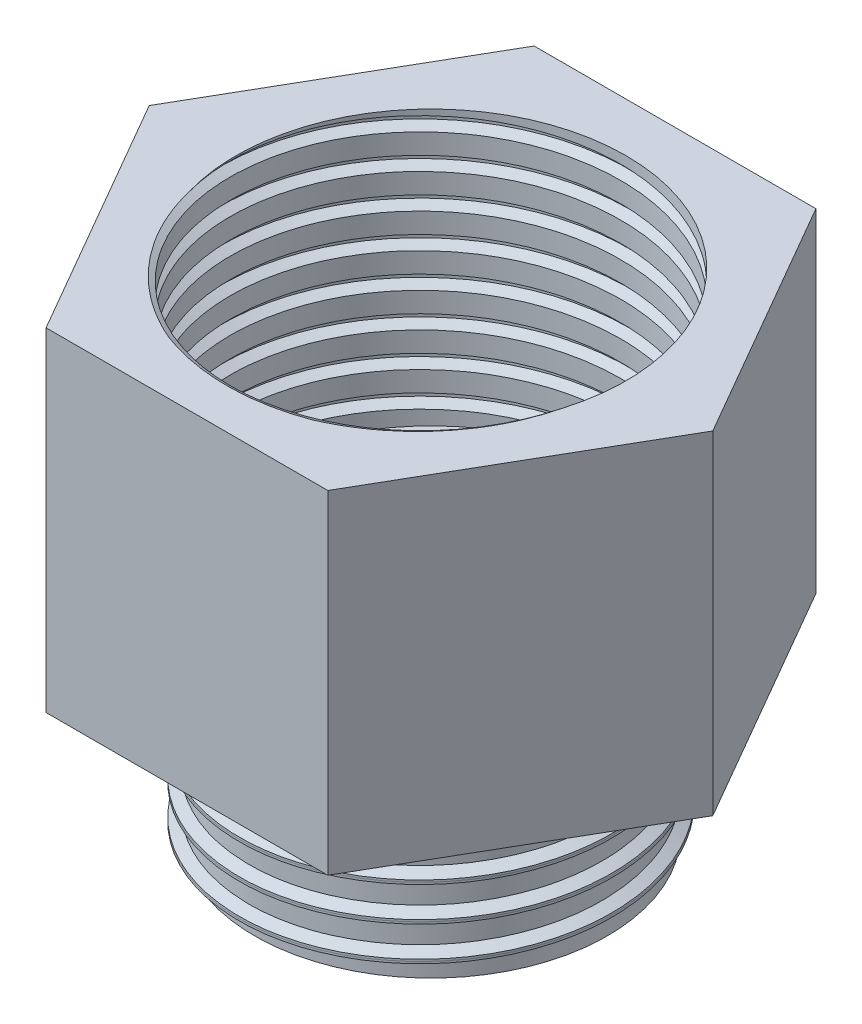
SolidWorks part; units mm, degrees
ref_plane "Front Plane" through (0, 0, 0) normal (0, 0, 1) x (1, 0, 0)
ref_plane "Top Plane" through (0, 0, 0) normal (0, 1, 0) x (1, 0, 0)
ref_plane "Right Plane" through (0, 0, 0) normal (1, 0, 0) x (0, 0, -1)
sketch "base-cap" plane through (0, 0, 0) normal (0, 1, 0) x (1, 0, 0)
  circle A0 centre (0, 0) radius 12.39
  circle A1 centre (0, 0) radius 5
  circle A2 centre (0, 0) radius 9
  dimension "D1" = 24.78
  dimension "D2" = 10
  dimension "D3" = 18
extrude "bottom-rim" add sketch "base-cap" against normal blind 8 contours A2 | A1
sketch "base-hex-inner" plane through (0, 0, 0) normal (0, 1, 0) x (1, 0, 0)
  line L0 (-7.188, -12.45) -> (7.188, 12.45) construction
  line L1 (-7.188, -12.45) -> (7.188, -12.45)
  line L2 (7.188, -12.45) -> (14.376, 0)
  line L3 (14.376, 0) -> (7.188, 12.45)
  line L4 (7.188, 12.45) -> (-7.188, 12.45)
  line L5 (-7.188, 12.45) -> (-14.376, 0)
  line L6 (-14.376, 0) -> (-7.188, -12.45)
  line L8 (14.376, 0) -> (-14.376, 0) construction
  circle A0 centre (0, 0) radius 9.95
  circle A1 centre (0, 0) radius 5
  circle A2 centre (0, 0) radius 7.67
  circle A3 centre (0, 0) radius 5 construction
  point P6 (0, 7.67)
  dimension "D1" = 12.45
  dimension "D3" = 12.45
  dimension "D4" = 19.9
  dimension "D5" = 10
  dimension "D2" = 4.78
extrude "hex-extrude" add sketch "base-hex-inner" along normal blind 17 contours L2 L3 L4 L5 L6 L1 | A0
sketch "thread" plane through (0, 17, 0) normal (0, 1, 0) x (1, 0, 0)
  line L1 (7.188, 12.45) -> (-7.188, 12.45) construction
  circle A0 centre (0, 0) radius 10.05
  point P5 (0, 10.05)
  point P6 (0, 12.45)
  dimension "D1" = 2.4
curve "inner-thread" pitch 1.75 height 14 turns 8
sketch "center" plane through (0, 0, 0) normal (1, 0, 0) x (0, 0, -1)
  line L0 (0, 18.39) -> (0, -4.4949) construction
sketch "ref-cut" plane through (0, 17, 0) normal (0, 1, 0) x (1, 0, 0)
  line L0 (0, -12.45) -> (0, 12.45) construction
  line L1 (-7.188, -12.45) -> (7.188, -12.45) construction
  line L2 (7.188, 12.45) -> (-7.188, 12.45) construction
  circle A0 centre (0, 0) radius 9.95 construction
  point P6 (0, -9.95)
  point P7 (0, 0)
sketch "cut" plane through (0, 0, 0) normal (1, 0, 0) x (0, 0, -1)
  line L0 (-10.05, 17) -> (-9.7036, 17) construction
  line L1 (-12.45, 17) -> (12.45, 17) construction
  line L2 (-9.7036, 17) -> (-9.7036, 17.5)
  line L3 (-9.7036, 17.5) -> (-10.3964, 17.1)
  line L4 (-10.3964, 17.1) -> (-10.3964, 16.9)
  line L5 (-10.3964, 16.9) -> (-9.7036, 16.5)
  line L6 (-9.7036, 16.5) -> (-9.7036, 17)
  line L7 (-10.05, 17) -> (-10.3964, 17) construction
  spline S0 degree 3 poles (-10.05, 17) (-10.05, 16.9638) (-9.5267, 16.8905) (-7.2914, 16.7813) (-3.9461, 16.6719) (0, 16.5625) (3.9461, 16.4531) (7.2914, 16.3438) (9.5267, 16.2344) (10.3116, 16.125) (9.5267, 16.0156) (7.2914, 15.9063) (3.9461, 15.7969) (0, 15.6875) (-3.9461, 15.5781) (-7.2914, 15.4688) (-9.5267, 15.3594) (-10.3116, 15.25) (-9.5267, 15.1406) (-7.2914, 15.0313) (-3.9461, 14.9219) (0, 14.8125) (3.9461, 14.7031) (7.2914, 14.5937) (9.5267, 14.4844) (10.3116, 14.375) (9.5267, 14.2656) (7.2914, 14.1563) (3.9461, 14.0469) (0, 13.9375) (-3.9461, 13.8281) (-7.2914, 13.7187) (-9.5267, 13.6094) (-10.3116, 13.5) (-9.5267, 13.3906) (-7.2914, 13.2812) (-3.9461, 13.1719) (0, 13.0625) (3.9461, 12.9531) (7.2914, 12.8437) (9.5267, 12.7344) (10.3116, 12.625) (9.5267, 12.5156) (7.2914, 12.4062) (3.9461, 12.2969) (0, 12.1875) (-3.9461, 12.0781) (-7.2914, 11.9687) (-9.5267, 11.8594) (-10.3116, 11.75) (-9.5267, 11.6406) (-7.2914, 11.5312) (-3.9461, 11.4219) (0, 11.3125) (3.9461, 11.2031) (7.2914, 11.0937) (9.5267, 10.9844) (10.3116, 10.875) (9.5267, 10.7656) (7.2914, 10.6562) (3.9461, 10.5469) (0, 10.4375) (-3.9461, 10.3281) (-7.2914, 10.2187) (-9.5267, 10.1094) (-10.3116, 10) (-9.5267, 9.8906) (-7.2914, 9.7812) (-3.9461, 9.6719) (0, 9.5625) (3.9461, 9.4531) (7.2914, 9.3437) (9.5267, 9.2344) (10.3116, 9.125) (9.5267, 9.0156) (7.2914, 8.9062) (3.9461, 8.7969) (0, 8.6875) (-3.9461, 8.5781) (-7.2914, 8.4687) (-9.5267, 8.3594) (-10.3116, 8.25) (-9.5267, 8.1406) (-7.2914, 8.0312) (-3.9461, 7.9219) (0, 7.8125) (3.9461, 7.7031) (7.2914, 7.5937) (9.5267, 7.4844) (10.3116, 7.375) (9.5267, 7.2656) (7.2914, 7.1562) (3.9461, 7.0469) (0, 6.9375) (-3.9461, 6.8281) (-7.2914, 6.7187) (-9.5267, 6.6094) (-10.3116, 6.5) (-9.5267, 6.3906) (-7.2914, 6.2812) (-3.9461, 6.1719) (0, 6.0625) (3.9461, 5.9531) (7.2914, 5.8437) (9.5267, 5.7344) (10.3116, 5.625) (9.5267, 5.5156) (7.2914, 5.4062) (3.9461, 5.2969) (0, 5.1875) (-3.9461, 5.0781) (-7.2914, 4.9687) (-9.5267, 4.8594) (-10.3116, 4.75) (-9.5267, 4.6406) (-7.2914, 4.5312) (-3.9461, 4.4219) (0, 4.3125) (3.9461, 4.2031) (7.2914, 4.0937) (9.5267, 3.9844) (10.3116, 3.875) (9.5267, 3.7656) (7.2914, 3.6562) (3.9461, 3.5469) (0, 3.4375) (-3.9461, 3.3281) (-7.2914, 3.2187) (-9.5267, 3.1095) (-10.05, 3.0362) (-10.05, 3) knots 0 0 0 0 0.007813 0.015625 0.023438 0.03125 0.039063 0.046875 0.054688 0.0625 0.070313 0.078125 0.085938 0.09375 0.101563 0.109375 0.117188 0.125 0.132813 0.140625 0.148438 0.15625 0.164063 0.171875 0.179688 0.1875 0.195313 0.203125 0.210938 0.21875 0.226563 0.234375 0.242188 0.25 0.257813 0.265625 0.273438 0.28125 0.289063 0.296875 0.304688 0.3125 0.320313 0.328125 0.335938 0.34375 0.351563 0.359375 0.367188 0.375 0.382813 0.390625 0.398438 0.40625 0.414063 0.421875 0.429688 0.4375 0.445313 0.453125 0.460938 0.46875 0.476563 0.484375 0.492188 0.5 0.507813 0.515625 0.523438 0.53125 0.539063 0.546875 0.554688 0.5625 0.570313 0.578125 0.585938 0.59375 0.601563 0.609375 0.617188 0.625 0.632813 0.640625 0.648438 0.65625 0.664063 0.671875 0.679688 0.6875 0.695313 0.703125 0.710938 0.71875 0.726563 0.734375 0.742188 0.75 0.757813 0.765625 0.773438 0.78125 0.789063 0.796875 0.804688 0.8125 0.820313 0.828125 0.835938 0.84375 0.851563 0.859375 0.867188 0.875 0.882813 0.890625 0.898438 0.90625 0.914063 0.921875 0.929688 0.9375 0.945313 0.953125 0.960938 0.96875 0.976563 0.984375 0.992188 1 1 1 1 construction
  dimension "D1" = 60
  dimension "D2" = 0.2
  dimension "D3" = 0.5
sketch "spira" plane through (0, -8, 0) normal (0, -1, 0) x (1, 0, 0)
  circle A0 centre (0, 0) radius 9
  dimension "D1" = 18
curve "Helix/Spiral1" pitch 1.75 height 7.875 radius 9 centre (0, -8, 0) axis (0, 1, 0) start towards (0, 0, -1)
sketch "extrude out" plane through (0, 0, 0) normal (1, 0, 0) x (0, 0, -1)
  line L0 (9, -8) -> (9.5, -8) construction
  line L1 (9.5, -8) -> (9.5, -8.0992)
  line L2 (9.5, -8.0992) -> (9, -8.3879)
  line L3 (9, -8.3879) -> (9, -7.6121)
  line L4 (9, -7.6121) -> (9.5, -7.9008)
  line L5 (9.5, -7.9008) -> (9.5, -8)
  spline S0 degree 3 poles (9, -8) (9, -7.9638) (8.5314, -7.8905) (6.5296, -7.7813) (3.5338, -7.6719) (0, -7.5625) (-3.5338, -7.4531) (-6.5296, -7.3438) (-8.5314, -7.2344) (-9.2343, -7.125) (-8.5314, -7.0156) (-6.5296, -6.9063) (-3.5338, -6.7969) (0, -6.6875) (3.5338, -6.5781) (6.5296, -6.4688) (8.5314, -6.3594) (9.2343, -6.25) (8.5314, -6.1406) (6.5296, -6.0313) (3.5338, -5.9219) (0, -5.8125) (-3.5338, -5.7031) (-6.5296, -5.5938) (-8.5314, -5.4844) (-9.2343, -5.375) (-8.5314, -5.2656) (-6.5296, -5.1562) (-3.5338, -5.0469) (0, -4.9375) (3.5338, -4.8281) (6.5296, -4.7187) (8.5314, -4.6094) (9.2343, -4.5) (8.5314, -4.3906) (6.5296, -4.2812) (3.5338, -4.1719) (0, -4.0625) (-3.5338, -3.9531) (-6.5296, -3.8437) (-8.5314, -3.7344) (-9.2343, -3.625) (-8.5314, -3.5156) (-6.5296, -3.4062) (-3.5338, -3.2969) (0, -3.1875) (3.5338, -3.0781) (6.5296, -2.9687) (8.5314, -2.8594) (9.2343, -2.75) (8.5314, -2.6406) (6.5296, -2.5312) (3.5338, -2.4219) (0, -2.3125) (-3.5338, -2.2031) (-6.5296, -2.0937) (-8.5314, -1.9844) (-9.2343, -1.875) (-8.5314, -1.7656) (-6.5296, -1.6562) (-3.5338, -1.5469) (0, -1.4375) (3.5338, -1.3281) (6.5296, -1.2187) (8.5314, -1.1094) (9.2343, -1) (8.5314, -0.8906) (6.5296, -0.7812) (3.5338, -0.6719) (0, -0.5625) (-3.5338, -0.4531) (-6.5296, -0.3437) (-8.5314, -0.2345) (-9, -0.1612) (-9, -0.125) knots 0 0 0 0 0.013889 0.027778 0.041667 0.055556 0.069444 0.083333 0.097222 0.111111 0.125 0.138889 0.152778 0.166667 0.180556 0.194444 0.208333 0.222222 0.236111 0.25 0.263889 0.277778 0.291667 0.305556 0.319444 0.333333 0.347222 0.361111 0.375 0.388889 0.402778 0.416667 0.430556 0.444444 0.458333 0.472222 0.486111 0.5 0.513889 0.527778 0.541667 0.555556 0.569444 0.583333 0.597222 0.611111 0.625 0.638889 0.652778 0.666667 0.680556 0.694444 0.708333 0.722222 0.736111 0.75 0.763889 0.777778 0.791667 0.805556 0.819444 0.833333 0.847222 0.861111 0.875 0.888889 0.902778 0.916667 0.930556 0.944444 0.958333 0.972222 0.986111 1 1 1 1 construction
  point P5 (0, 0)
  dimension "D1" = 60
  dimension "D2" = 0.0992
  dimension "D3" = 0.5
sweep "outside" add profiles "extrude out" path "Helix/Spiral1"
sketch "cap" plane through (0, -8, 0) normal (0, -1, 0) x (1, 0, 0)
  line L0 (0, 12.45) -> (0, -12.45) construction
  line L1 (7.188, 12.45) -> (-7.188, -12.45) construction
  line L2 (-7.188, 12.45) -> (7.188, -12.45) construction
  line L3 (6.0333, 10.45) -> (-6.0333, 10.45)
  line L4 (-6.0333, 10.45) -> (-12.0666, 0)
  line L5 (-12.0666, 0) -> (-6.0333, -10.45)
  line L6 (-6.0333, -10.45) -> (6.0333, -10.45)
  line L7 (6.0333, 10.45) -> (12.0666, 0)
  line L8 (12.0666, 0) -> (6.0333, -10.45)
  line L9 (7.188, 12.45) -> (14.376, 0) construction
  circle A0 centre (0, 0) radius 9
  circle A1 centre (0, 0) radius 6
  dimension "D1" = 18
  dimension "D3" = 12
  dimension "D2" = 2
extrude "iner" add sketch "base-hex-inner<6>" along normal blind 3 contours A0 | A1
sketch "base-hex-inner<6>" plane through (0, 0, 0) normal (0, 1, 0) x (1, 0, 0) same geometry as "base-hex-inner"
sketch "Sketch8" plane through (0, 17, 0) normal (0, 1, 0) x (1, 0, 0)
  circle A0 centre (0, 0) radius 9.95
  dimension "D1" = 19.9
curve "Helix/Spiral3" pitch 1.75 height 14 radius 9.95 centre (0, 17, 0) axis (0, -1, 0) start towards (0, 0, 1)
sweep "Cut-Sweep2" cut profiles "cut" path "Helix/Spiral3" align with end faces yes
